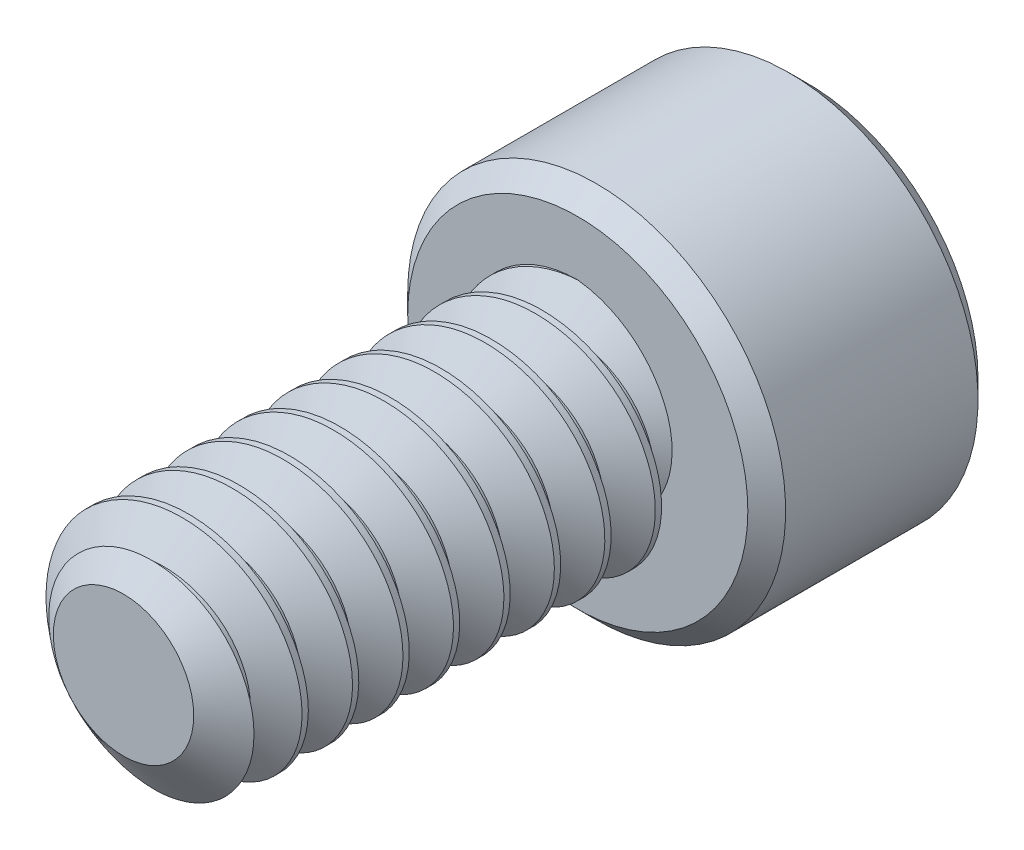
SolidWorks part; units mm, degrees
ref_plane "Front Plane" through (0, 0, 0) normal (0, 0, 1) x (1, 0, 0)
ref_plane "Top Plane" through (0, 0, 0) normal (0, 1, 0) x (1, 0, 0)
ref_plane "Right Plane" through (0, 0, 0) normal (1, 0, 0) x (0, 0, -1)
sketch "Sketch1" plane through (0, 0, 0) normal (0, 0, 1) x (1, 0, 0)
  circle A0 centre (0, 0) radius 2.413
  dimension "OD" = 4.826
extrude "Extrude1" add sketch "Sketch1" against normal blind 9.525
sketch "Sketch2" plane through (0, 0, 0) normal (0, 0, 1) x (1, 0, 0)
  circle A0 centre (0, 0) radius 2.413 construction
  circle A1 centre (0, 0) radius 2.413
curve "Helix/Spiral1" pitch 1.0583 height 10.5833 turns 10 parameters "pitch"=1.0583
sketch "Sketch3" plane through (0, 0, 0) normal (1, 0, 0) x (0, 0, -1)
  line L0 (-0.926, 2.413) -> (-0.5292, 1.7256)
  line L1 (-0.5292, 1.7256) -> (-0.3969, 1.7256)
  line L2 (-0.3969, 1.7256) -> (0, 2.413)
  line L3 (-0.926, 2.413) -> (0, 2.413)
  line L4 (-0.463, 2.413) -> (-0.463, 1.7256) construction
  line L5 (-0.7276, 2.0693) -> (-0.1984, 2.0693) construction
  line L6 (0, 2.413) -> (0, -2.413) construction
  dimension "D1" = 0.1323
  dimension "D2" = 0.5292
  dimension "D3" = 60
sweep "Cut-Sweep1" cut profiles "Sketch3" path "Helix/Spiral1"
sketch "Sketch4" plane through (0, 0, 0) normal (1, 0, 0) x (0, 0, -1)
  line L0 (0.6592, 2.413) -> (0, 1.4716)
  line L1 (0, 1.4716) -> (0, 2.413)
  line L2 (0.6592, 2.413) -> (0, 2.413)
  line L3 (-0.926, 2.413) -> (0, 2.413) construction
  line L4 (0, 0) -> (7.0209, 0) construction
  dimension "D1" = 55
  dimension "D2" = 0.254
revolve "Cut-Revolve1" cut sketch "Sketch4" angle 360 about L4
sketch "Sketch5" plane through (0, 0, 0) normal (1, 0, 0) x (0, 0, -1)
  line L0 (9.525, -1.7471) -> (9.525, 1.7217) construction
  line L1 (9.525, 2.54) -> (15.9635, 2.54)
  line L2 (9.525, 2.54) -> (9.525, 0)
  line L3 (9.525, 0) -> (15.875, 0)
  line L4 (15.875, 2.2098) -> (15.875, 0)
  line L5 (15.9635, 2.54) -> (15.875, 2.2098)
  line L6 (0, 0) -> (9.9695, 0) construction
  point P3 (15.875, 2.54)
  point P10 (15.875, 2.54)
  dimension "D1" = 0.3302
  dimension "Thread min" = 15.875
  dimension "D2" = 0.127
  dimension "D3" = 15
revolve "partially thread" [suppressed] add sketch "Sketch5" angle 360 about L6
sketch "Sketch6" plane through (0, 0, -9.525) normal (0, 0, -1) x (-1, 0, 0)
  circle A0 centre (0, 0) radius 3.9624
  dimension "head dia" = 7.9248
extrude "Extrude2" add sketch "Sketch6" along normal blind 4.826
sketch "Sketch7" plane through (0, 0, -14.351) normal (0, 0, -1) x (-1, 0, 0)
  line L1 (0, 2.2914) -> (-1.9844, 1.1457)
  line L2 (-1.9844, 1.1457) -> (-1.9844, -1.1457)
  line L3 (-1.9844, -1.1457) -> (0, -2.2914)
  line L4 (0, -2.2914) -> (1.9844, -1.1457)
  line L5 (1.9844, -1.1457) -> (1.9844, 1.1457)
  line L6 (1.9844, 1.1457) -> (0, 2.2914)
  circle A0 centre (0, 0) radius 1.9844 construction
  dimension "hex dia" = 3.9688
extrude "Cut-Extrude1" cut sketch "Sketch7" against normal blind 2.9766
sketch "Sketch8" plane through (0, 0, -14.351) normal (0, 0, -1) x (-1, 0, 0)
  circle A0 centre (0, 0) radius 2.2914
extrude "Cut-Extrude2" cut sketch "Sketch8" against normal through all draft 45
chamfer "Chamfer1" distance 0.3962 angle 45 2 edges at (-3.9624, 0, -14.351) (-3.9624, 0, -9.525)
sketch "Sketch9" plane through (0, 0, 0) normal (1, 0, 0) x (0, 0, -1)
  line L0 (0, 2.413) -> (0, -2.413) construction
  line L1 (11.1125, 2.413) -> (11.1125, -2.413) construction
  dimension "D1" = 11.1125
equation "\"D3@Helix/Spiral1\" = \"screw length@Extrude1\"+\"pitch@Helix/Spiral1\""
equation "\"D1@Sketch3\" = \"pitch@Helix/Spiral1\"*.125"
equation "\"D2@Sketch3\" = \"pitch@Helix/Spiral1\"*.5"
equation "\"D1@Cut-Extrude1\" = \"hex dia@Sketch7\"*.75"
equation "\"D1@Chamfer1\" = \"head dia@Sketch6\"*.05"
equation "\"D1@Sketch9\" = \"pitch@Helix/Spiral1\"*10.5"
